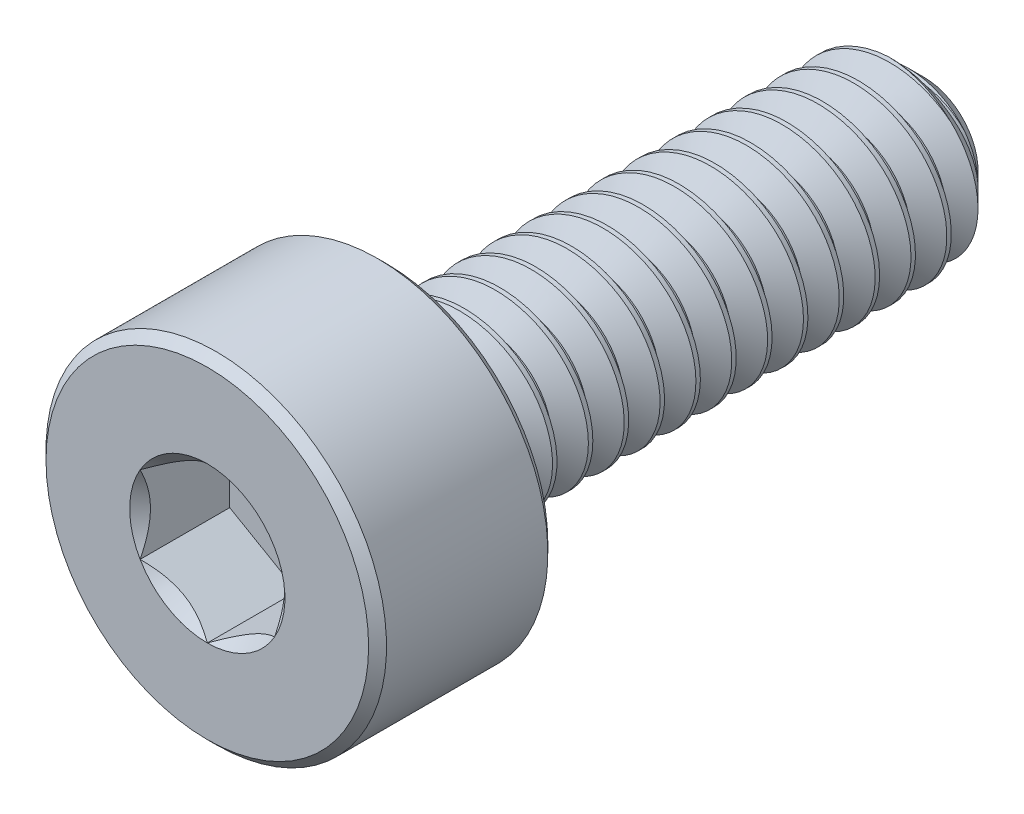
SolidWorks part; units mm, degrees
ref_plane "Front Plane" through (0, 0, 0) normal (0, 0, 1) x (1, 0, 0)
ref_plane "Top Plane" through (0, 0, 0) normal (0, 1, 0) x (1, 0, 0)
ref_plane "Right Plane" through (0, 0, 0) normal (1, 0, 0) x (0, 0, -1)
sketch "Sketch1" plane through (0, 0, 0) normal (1, 0, 0) x (0, 0, -1)
  line L0 (-4, 0) -> (4, 0) construction
  line L1 (4, 0) -> (4, 0.6) construction
  line L2 (4, 0.6) -> (3.6, 1) construction
  line L3 (3.6, 1) -> (3.7, 1) construction
  line L4 (3.7, 1) -> (-2, 1) construction
  line L5 (-2, 1) -> (-2, 1.9) construction
  line L6 (-2, 1.9) -> (-4, 1.9) construction
  line L7 (-4, 1.9) -> (-4, 0) construction
  line L8 (4, 0.6) -> (4, 1) construction
  line L9 (3.975, 1.0433) -> (4.175, 0.6969) construction
  line L10 (4.175, 0.6969) -> (4.375, 1.0433) construction
  line L11 (4.375, 1.0433) -> (3.975, 1.0433) construction
  line L12 (4.175, 1.0433) -> (4.175, 1) construction
  line L13 (4.175, 0.6969) -> (4.175, 0.7402) construction
  line L14 (4.15, 0.7402) -> (4.2, 0.7402) construction
  line L15 (4, 1) -> (4.35, 1) construction
  line L16 (3.9875, 1.0217) -> (4.3625, 1.0217) construction
  line L17 (4, 0) -> (4, -1) construction
  line L18 (-2.1, 1.9) -> (-2, 1.8) construction
  line L19 (-3.9, 1.9) -> (-4, 1.8) construction
  line L20 (-2, 1) -> (-2, 0) construction
  line L21 (-2, 0.5) -> (0, 0.5) construction
  line L22 (0, 0.5) -> (2, 0.5) construction
  line L23 (2, 0.5) -> (4, 0.5) construction
  line L24 (0, 0.5) -> (0, 1) construction
  line L25 (0, 1) -> (0, 1.9) construction
  line L26 (2, 0.5) -> (2, 1.9) construction
  point P0 (-4, 0.75)
  point P3 (3, 1)
  point P4 (0, 0)
  point P18 (2, 1)
  point P22 (4.175, 0.7402)
  point P24 (3.7, 1)
  point P25 (4.175, 1)
  point P28 (4.175, 1.0217)
  point P29 (3, -1)
  point P30 (0, 1)
  point P31 (-3, 1.9)
  point P37 (-2.35, 1.9)
  point P38 (-3.85, 1.9)
  point P45 (0, 0.5)
  point P46 (2, 0.5)
  dimension "D1" = 45
  dimension "D2" = 0.05
  dimension "D3" = 0.4
  dimension "D7" = 0.1
  dimension "D8" = 0.1
  dimension "D9" = 0.1
  dimension "D10" = 0.05
  dimension "D11" = 0.25
  dimension "Drive Size" = 1.5
  dimension "Head Diameter" = 3.8
  dimension "Head Height" = 2
  dimension "Thread Pitch" = 0.4
  dimension "Thread Major Diameter" = 2
  dimension "Length" = 6
  dimension "D12" = 0.3
  dimension "D4" = 1
sketch "Sketch2" plane through (0, 0, 0) normal (1, 0, 0) x (0, 0, -1)
  line L0 (-4, 0) -> (-4, 1.8)
  line L1 (-3.9, 1.9) -> (-2.1, 1.9)
  line L2 (-2, 1.8) -> (-2, 1)
  line L3 (-2, 1) -> (3.6, 1)
  line L4 (3.6, 1) -> (4, 0.6)
  line L5 (4, 0.6) -> (4, 0)
  line L6 (-2.1, 1.9) -> (-2, 1.8) construction
  line L7 (4, 0) -> (-4, 0)
  line L8 (-3.9, 1.9) -> (-4, 1.8) construction
  line L9 (-2.1, 1.9) -> (-2, 1.8)
  line L10 (-3.9, 1.9) -> (-4, 1.8)
revolve "Revolve1" add sketch "Sketch2" angle 360 about L7
sketch "Sketch3" plane through (0, 0, 4) normal (0, 0, 1) x (1, 0, 0)
  line L1 (0.75, -0.433) -> (0.75, 0.433)
  line L2 (0.75, 0.433) -> (0, 0.866)
  line L3 (0, 0.866) -> (-0.75, 0.433)
  line L4 (-0.75, 0.433) -> (-0.75, -0.433)
  line L5 (-0.75, -0.433) -> (0, -0.866)
  line L6 (0, -0.866) -> (0.75, -0.433)
  circle A0 centre (0, 0) radius 0.75 construction
extrude "Cut-Extrude1" cut sketch "Sketch3" against normal offset from surface (1 mm away) 1 up to face at (0, 1.8, 2)
sketch "Sketch4" plane through (0, 0, 4) normal (0, 0, 1) x (1, 0, 0)
  circle A0 centre (0, 0) radius 0.866
extrude "Cut-Extrude2" cut sketch "Sketch4" against normal up to vertex (1 mm away) draft 45 up to point (0, 1.9, 3)
ref_plane "Plane1" through (0, 0, -3.7) normal (0, 0, 1) x (1, 0, 0)
split "Split1" bodies to split 106 resulting bodies 107 108 split by face at (0, 1.8, 2)
sketch "Sketch6" plane through (0, 0, -4) normal (0, 0, -1) x (-1, 0, 0)
  circle A0 centre (0, 0) radius 1
curve "Helix/Spiral1" pitch 0.4 height 6.46 radius 1 centre (0, 0, -4) axis (0, 0, 1) start towards (0, 1, 0)
sketch "Sketch7" plane through (0, 0, 0) normal (1, 0, 0) x (0, 0, -1)
  line L0 (3.9875, 1.0217) -> (4.3625, 1.0217)
  line L1 (4.3625, 1.0217) -> (4.2, 0.7402)
  line L2 (4.2, 0.7402) -> (4.15, 0.7402)
  line L3 (4.15, 0.7402) -> (3.9875, 1.0217)
sweep "Cut-Sweep1" cut profiles "Sketch7" path "Helix/Spiral1" align with end faces yes
sketch "Sketch8" plane through (0, 0, 2) normal (0, 0, -1) x (-1, 0, 0)
  circle A0 centre (0, 0) radius 1
extrude "Boss-Extrude1" add sketch "Sketch8" along normal through all draft 45
equation "\"D2@Sketch1\" = \"Thread Pitch@Sketch1\" / 8"
equation "\"D3@Sketch1\"= \"Thread Pitch@Sketch1\""
equation "\"D4@Helix/Spiral1\" = \"Thread Pitch@Sketch1\""
equation "\"D7@Sketch1\" = \"Head Height@Sketch1\" * .05"
equation "\"D8@Sketch1\"=\"D7@Sketch1\""
equation "\"D9@Sketch1\"=\"D7@Sketch1\""
equation "\"D10@Sketch1\"=\"D7@Sketch1\"/2"
equation "\"D11@Sketch1\"=\"D10@Sketch1\"*5"
equation "\"D4@Sketch1\"=\"Thread Pitch@Sketch1\"*2.5"
equation "\"D12@Sketch1\"=\"Thread Pitch@Sketch1\"*.75"
